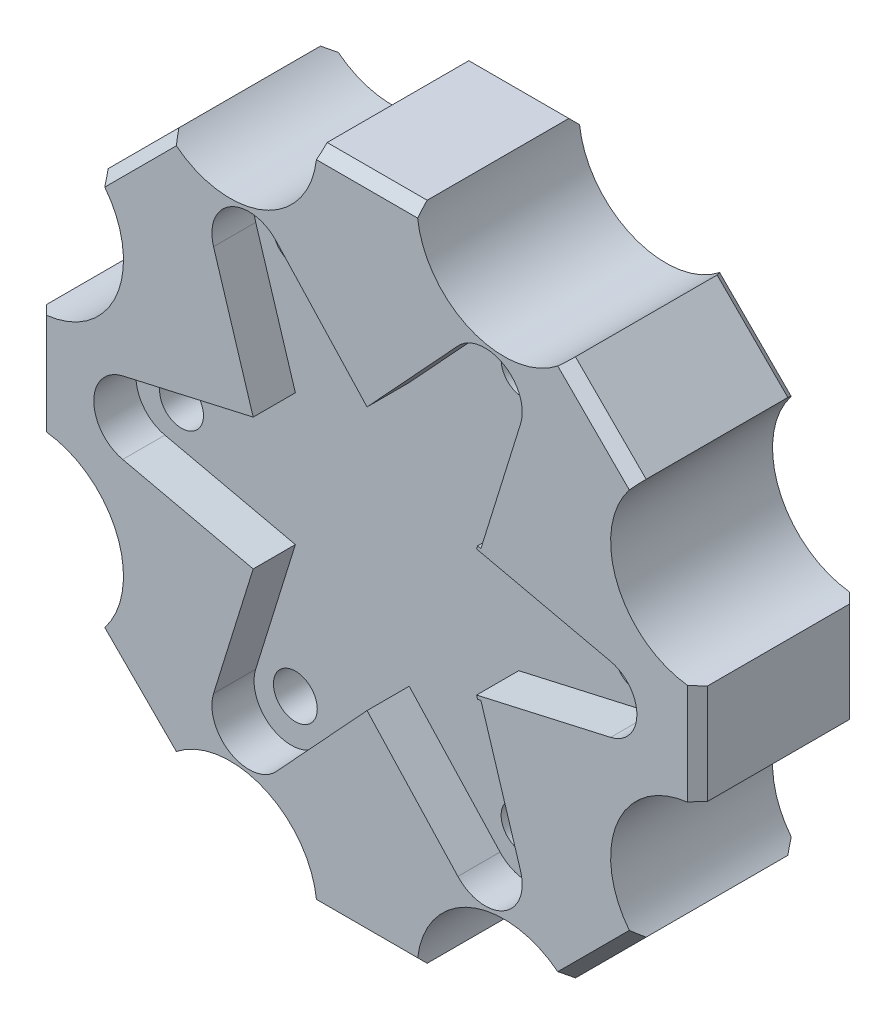
SolidWorks part; units mm, degrees
ref_plane "Front Plane" through (0, 0, 0) normal (0, 0, 1) x (1, 0, 0)
ref_plane "Top Plane" through (0, 0, 0) normal (0, 1, 0) x (1, 0, 0)
ref_plane "Right Plane" through (0, 0, 0) normal (1, 0, 0) x (0, 0, -1)
sketch "Sketch1" plane through (0, 0, 0) normal (0, 0, 1) x (1, 0, 0)
  line L1 (-8.115, -19.5913) -> (8.115, -19.5913)
  line L2 (8.115, -19.5913) -> (19.5913, -8.115)
  line L3 (19.5913, -8.115) -> (19.5913, 8.115)
  line L4 (19.5913, 8.115) -> (8.115, 19.5913)
  line L5 (8.115, 19.5913) -> (-8.115, 19.5913)
  line L6 (-8.115, 19.5913) -> (-19.5913, 8.115)
  line L7 (-19.5913, 8.115) -> (-19.5913, -8.115)
  line L8 (-19.5913, -8.115) -> (-8.115, -19.5913)
  circle A0 centre (0, 0) radius 19.5913 construction
  circle A1 centre (-8.115, 19.5913) radius 4.95 construction
  circle A2 centre (8.115, 19.5913) radius 4.95 construction
  arc A3 (-11.7566, 15.9497) -> (-2.965, 19.5913) centre (-8.115, 19.5913) ccw
  arc A4 (2.965, 19.5913) -> (11.7566, 15.9497) centre (8.115, 19.5913) ccw
  arc A5 (15.9497, 11.7566) -> (19.5913, 2.965) centre (19.5913, 8.115) ccw
  circle A6 centre (-8.115, 19.5913) radius 5.15 construction
  circle A7 centre (8.115, 19.5913) radius 5.15 construction
  arc A8 (19.5913, -2.965) -> (15.9497, -11.7566) centre (19.5913, -8.115) ccw
  arc A9 (11.7566, -15.9497) -> (2.965, -19.5913) centre (8.115, -19.5913) ccw
  arc A10 (-2.965, -19.5913) -> (-11.7566, -15.9497) centre (-8.115, -19.5913) ccw
  arc A11 (-15.9497, -11.7566) -> (-19.5913, -2.965) centre (-19.5913, -8.115) ccw
  arc A12 (-19.5913, 2.965) -> (-15.9497, 11.7566) centre (-19.5913, 8.115) ccw
  point P15 (13.265, 19.5913)
  point P18 (-2.965, 19.5913)
  point P44 (0, 0)
  dimension "D2" = 9.9
  dimension "D1" = 16.23
  dimension "D3" = 0.2
  dimension "D4" = 4
extrude "Boss-Extrude1" add sketch "Sketch1" along normal blind 9.6 contours A12 L7 A11 L8 A10 L1 A9 L2 A8 L3 A5 L4 A4 L5 A3 L6 region at (0, 0, 0)
chamfer "Chamfer2" distance 0.6 angle 45 16 edges at (0, -19.5913, 0) (-13.8532, -13.8532, 0) (-19.5913, 0, 0) (-13.8532, 13.8532, 0) (0, 19.5913, 0) (13.8532, 13.8532, 0) (19.5913, 0, 0) (13.8532, -13.8532, 0) (-13.8532, 13.8532, 9.6) (0, 19.5913, 9.6) (13.8532, 13.8532, 9.6) (19.5913, 0, 9.6) (13.8532, -13.8532, 9.6) (0, -19.5913, 9.6) (-13.8532, -13.8532, 9.6) (-19.5913, 0, 9.6)
sketch "Sketch3" plane through (0, 0, 9.6) normal (0, 0, 1) x (1, 0, 0)
  line L0 (0, 0) -> (-2.5, 0) construction
  line L1 (-2.5, 0) -> (-5.5, 0) construction
  line L2 (-2, -1.5) -> (-5.5, -1.5)
  line L3 (-5.5, -1.5) -> (-5.5, 1.5)
  line L4 (-5.5, 1.5) -> (-2, 1.5)
  line L5 (0, 2.5) -> (0, -2.5) construction
  line L6 (5.5, 1.5) -> (2, 1.5)
  line L7 (5.5, -1.5) -> (5.5, 1.5)
  line L8 (2, -1.5) -> (5.5, -1.5)
  arc A0 (-2, -1.5) -> (2, -1.5) centre (0, 0) ccw
  arc A1 (-2.5, 0) -> (-2, -1.5) centre (0, 0) ccw construction
  arc A2 (-2, 1.5) -> (-2.5, 0) centre (0, 0) ccw construction
  arc A3 (2, 1.5) -> (-2, 1.5) centre (0, 0) ccw
  arc A4 (2, -1.5) -> (2, 1.5) centre (0, 0) ccw construction
  point P1 (0, 0)
  point P13 (0, 0)
  dimension "D3" = 5
  dimension "D1" = 3
  dimension "D2" = 3
extrude "Cut-Extrude1" [suppressed] cut sketch "Sketch3" against normal through all
sketch "Sketch4" plane through (0, 0, 9.6) normal (0, 0, 1) x (1, 0, 0)
  line L0 (14.4417, 1.9506) -> (6.4952, 3.75)
  line L1 (14.4417, -1.9506) -> (6.4952, -3.75)
  line L2 (6.4952, -3.75) -> (6.4952, 3.75) construction
  line L3 (14, 0) -> (7.5, 0) construction
  line L4 (5.5316, -13.4822) -> (0, -7.5)
  line L5 (8.9101, -11.5316) -> (6.4952, -3.75)
  line L6 (-8.9101, -11.5316) -> (-6.4952, -3.75)
  line L7 (-5.5316, -13.4822) -> (0, -7.5)
  line L8 (-14.4417, 1.9506) -> (-6.4952, 3.75)
  line L9 (-14.4417, -1.9506) -> (-6.4952, -3.75)
  line L10 (-5.5316, 13.4822) -> (0, 7.5)
  line L11 (-8.9101, 11.5316) -> (-6.4952, 3.75)
  line L12 (8.9101, 11.5316) -> (6.4952, 3.75)
  line L13 (5.5316, 13.4822) -> (0, 7.5)
  line L14 (9.1011, -11.4723) -> (6.6862, -3.6907)
  line L15 (5.3847, -13.618) -> (0, -7.7946)
  line L16 (-5.3847, -13.618) -> (0, -7.7946)
  line L17 (-9.1011, -11.4723) -> (-6.7503, -3.8973)
  line L18 (-14.4859, -2.1457) -> (-6.7503, -3.8973)
  line L19 (-14.4859, 2.1457) -> (-6.7503, 3.8973)
  line L20 (-9.1011, 11.4723) -> (-6.7503, 3.8973)
  line L21 (-5.3847, 13.618) -> (0, 7.7946)
  line L22 (5.3847, 13.618) -> (0, 7.7946)
  line L23 (9.1011, 11.4723) -> (6.6862, 3.6907)
  line L24 (14.4859, 2.1457) -> (6.5394, 3.9451)
  line L25 (14.4859, -2.1457) -> (6.5394, -3.9451)
  arc A0 (14.4417, -1.9506) -> (14.4417, 1.9506) centre (14, 0) ccw
  circle A1 centre (0, 0) radius 7.5 construction
  arc A2 (5.5316, -13.4822) -> (8.9101, -11.5316) centre (7, -12.1244) ccw
  arc A3 (-8.9101, -11.5316) -> (-5.5316, -13.4822) centre (-7, -12.1244) ccw
  arc A4 (-14.4417, 1.9506) -> (-14.4417, -1.9506) centre (-14, 0) ccw
  arc A5 (-5.5316, 13.4822) -> (-8.9101, 11.5316) centre (-7, 12.1244) ccw
  arc A6 (8.9101, 11.5316) -> (5.5316, 13.4822) centre (7, 12.1244) ccw
  arc A7 (5.3847, -13.618) -> (9.1011, -11.4723) centre (7, -12.1244) ccw
  arc A8 (-9.1011, -11.4723) -> (-5.3847, -13.618) centre (-7, -12.1244) ccw
  arc A9 (-14.4859, 2.1457) -> (-14.4859, -2.1457) centre (-14, 0) ccw
  arc A10 (-5.3847, 13.618) -> (-9.1011, 11.4723) centre (-7, 12.1244) ccw
  arc A11 (9.1011, 11.4723) -> (5.3847, 13.618) centre (7, 12.1244) ccw
  arc A12 (14.4859, -2.1457) -> (14.4859, 2.1457) centre (14, 0) ccw
  point P3 (16, 0)
  point P37 (0, 0)
  dimension "D2" = 2
  dimension "D3" = 15
  dimension "D1" = 16
  dimension "D4" = 7.5
  dimension "D6" = 0.2
  dimension "D5" = 6
extrude "Cut-Extrude2" cut sketch "Sketch4" against normal blind 2.5 contours L12 A6 L13 L10 A5 L11 L8 A4 L9 L6 A3 L7 L4 A2 L5 L1 A0 L0 | L23 A11 L22 L21 A10 L20 L19 A9 L18 L17 A8 L16 L15 A7 L14 L25 L5 A2 L4 L7 A3 L6 L9 A4 L8 L11 A5 L10 L13 A6 L12 L24 region at (0, 0, 9.6) region at (6.737, 4.2929, 9.6)
hole_wizard "M2 Clearance Hole1" positions "Sketch7" profile "Sketch6" hole size "M2" standard "ANSI Metric" end condition through all
sketch "Sketch7" plane through (0, 0, 7.1) normal (0, 0, 1) x (1, 0, 0)
  line L0 (0, 0) -> (13.5, 0) construction
  point P0 (13.5, 0)
  point P10 (6.75, -11.6913)
  point P11 (-6.75, -11.6913)
  point P12 (-13.5, 0)
  point P13 (-6.75, 11.6913)
  point P14 (6.75, 11.6913)
  point P16 (0, 0)
  dimension "D1" = 13.5
  dimension "D2" = 6
sketch "Sketch6" plane through (13.5, 0, 7.1) normal (1, 0, 0) x (0, -1, 0)
  line L0 (0, 0) -> (0, 7.1)
  line L1 (0, 7.1) -> (1.3, 7.1)
  line L2 (1.3, 7.1) -> (1.3, 0)
  line L5 (1.3, 0) -> (0, 0)
  line L11 (0, -6.35) -> (0, 107.95) construction
  dimension "Thru Hole Dia." = 2.6
  dimension "Thru Hole Depth" = 7.1
extrude "Cut-Extrude3" cut sketch "Sketch3<2>" along normal blind 5.5 from surface starting at face at (14.8, 0, 0)
sketch "Sketch3<2>" plane through (0, 0, 9.6) normal (0, 0, 1) x (1, 0, 0) same geometry as "Sketch3"
